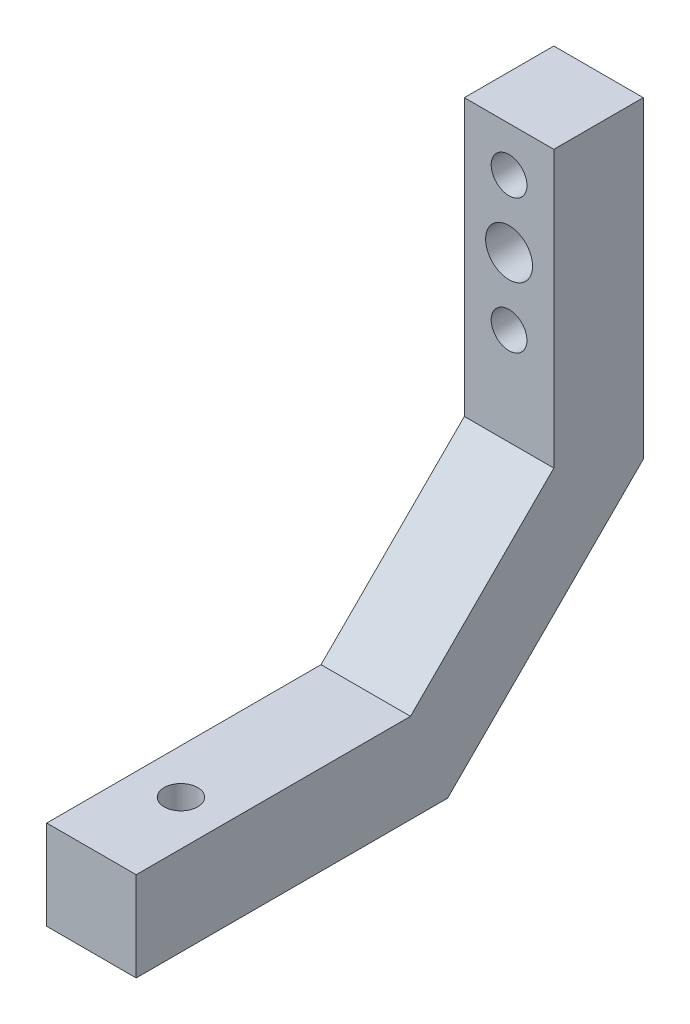
SolidWorks part; units mm, degrees
ref_plane "Front Plane" through (0, 0, 0) normal (0, 0, 1) x (1, 0, 0)
ref_plane "Top Plane" through (0, 0, 0) normal (0, 1, 0) x (1, 0, 0)
ref_plane "Right Plane" through (0, 0, 0) normal (1, 0, 0) x (0, 0, -1)
ref_axis "Z" through (0, 0, 47.607) along (0, 0, -1)
sketch "Sketch1" plane through (0, 0, 0) normal (1, 0, 0) x (0, 0, -1)
  line L0 (-8, 10) -> (0, 10)
  line L1 (0, 10) -> (0, -18)
  line L2 (0, -18) -> (-17.5, -35.5)
  line L3 (-17.5, -35.5) -> (-37.34, -35.5)
  line L4 (-37.34, -35.5) -> (-37.34, -27.5) construction
  line L5 (-37.34, -27.5) -> (-20.8137, -27.5)
  line L6 (-20.8137, -27.5) -> (-8, -14.6863)
  line L7 (-8, -14.6863) -> (-8, 10)
  line L8 (-13.4134, -20.0997) -> (-7.7566, -25.7566) construction
  line L10 (-37.34, -27.5) -> (-45.34, -27.5)
  line L11 (-37.34, -27.5) -> (-37.34, -35.5) construction
  line L12 (-37.34, -35.5) -> (-45.34, -35.5)
  line L13 (-45.34, -27.5) -> (-45.34, -35.5)
  dimension "D1" = 8
  dimension "D2" = 37.34
  dimension "D3" = 35.5
  dimension "D4" = 10
  dimension "D5" = 135
  dimension "D6" = 17.5
  dimension "D7" = 8
extrude "Boss-Extrude1" add sketch "Sketch1" along normal blind 4 and the other way blind 4
sketch "Sketch3" plane through (0, -27.5, 0) normal (0, 1, 0) x (1, 0, 0)
  line L0 (-4.4, 0) -> (4.4, 0) construction
  line L1 (0, -24.937) -> (0, 24.937) construction
  circle A0 centre (0, -37.34) radius 1.5
  dimension "D2" = 3
  dimension "D1" = 37.34
extrude "Cut-Extrude1" cut sketch "Sketch3" against normal through all
sketch "Sketch4" plane through (0, 0, 8) normal (0, 0, 1) x (1, 0, 0)
  line L0 (0, -6) -> (0, 6) construction
  circle A0 centre (0, 0) radius 2.1
  circle A1 centre (0, 6) radius 1.6
  circle A2 centre (0, -6) radius 1.6
  dimension "D1" = 4.2
  dimension "D3" = 3.2
  dimension "D2" = 12
extrude "Cut-Extrude2" cut sketch "Sketch4" against normal through all
ref_axis "Axis1" through (0, -27.5, 37.34) along (0, 1, 0)
equation "\"rbracket-width\"= 8"
equation "\"D1@Boss-Extrude1\"=\"rbracket-width\"/2"
equation "\"D2@Boss-Extrude1\"=\"rbracket-width\"/2"
equation "\"EyeCaptureRadius\"= ( \"EyeDiameter\" + \"EyeClearance\" ) / 2"
equation "\"rbracket_planetocenterline_dist\"= \"BasePlaneDistance\""
equation "\"D2@Sketch1\"=\"rbracket_planetocenterline_dist\""
equation "\"EyeDiameter\" = 35"
equation "\"BasePlaneDistance\" = \"EyeDiameter\"/2+19.84"
equation "\"EyeClearance\" = 2"
equation "\"D1@Sketch1\"=\"rbracket-width\""
equation "\"D3@Sketch1\"=(\"EyeDiameter\"+\"EyeClearance\"+\"EyeClearance\")/2 + \"L2Thickness\" + \"rbracket-width\""
equation "\"D4@Sketch1\"= 10"
equation "\"D6@Sketch1\"=\"EyeDiameter\"/2"
equation "\"D7@Sketch1\"=\"rbracket-width\""
equation "\"D1@Sketch3\"=\"BasePlaneDistance\""
equation "\"L2Thickness\" = 8"
